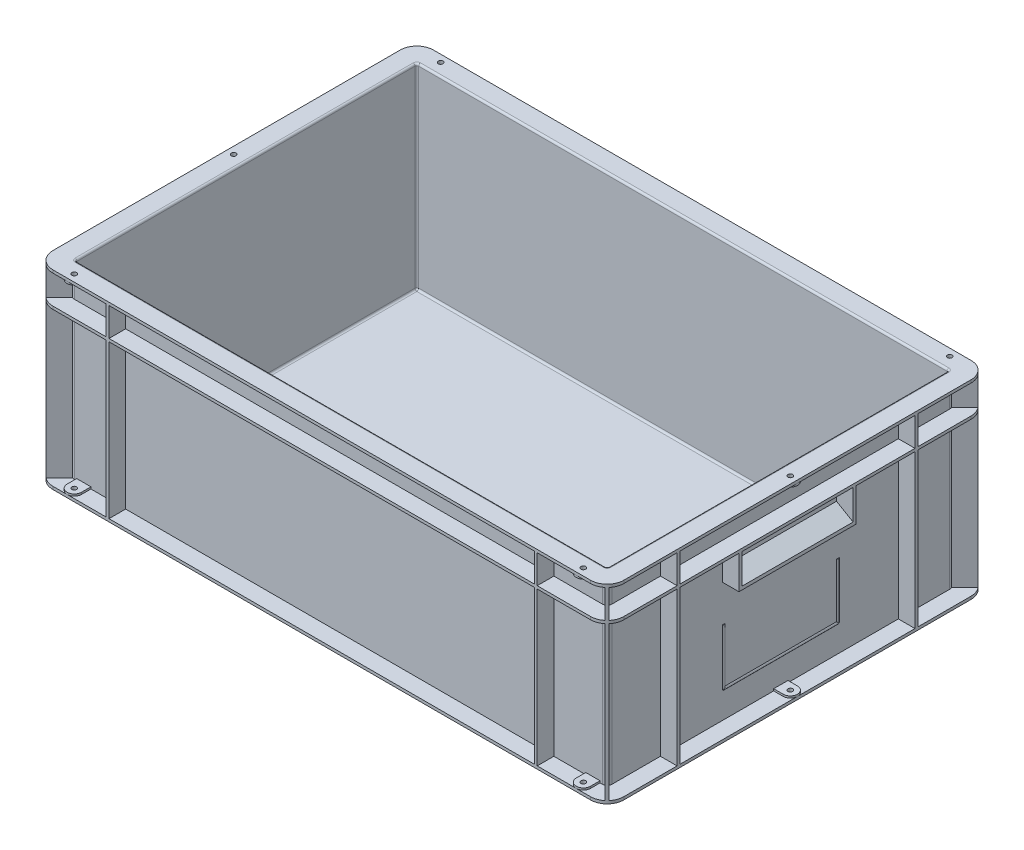
SolidWorks part; units mm, degrees
material "PTFE (général)"
ref_plane "Plan de face" through (0, 0, 0) normal (0, 0, 1) x (1, 0, 0)
ref_plane "Plan de dessus" through (0, 0, 0) normal (0, 1, 0) x (1, 0, 0)
ref_plane "Plan de côté" through (0, 0, 0) normal (1, 0, 0) x (0, 0, -1)
sketch "Esquisse vue de DESSUS" plane through (0, 0, 0) normal (0, 1, 0) x (1, 0, 0)
  line L0 (-300, 0) -> (300, 0) construction
  line L1 (-282.5, 200) -> (282.5, 200)
  line L2 (-300, 182.5) -> (-300, -182.5)
  line L3 (-282.5, -200) -> (282.5, -200)
  line L4 (300, 182.5) -> (300, -182.5)
  line L5 (-277.5, 182.5) -> (277.5, 182.5)
  line L6 (0, 200) -> (0, -200) construction
  line L7 (282.5, 177.5) -> (282.5, -177.5)
  line L8 (-277.5, -182.5) -> (277.5, -182.5)
  line L9 (-282.5, 177.5) -> (-282.5, -177.5)
  line L10 (-282.5, 182.5) -> (-294.8744, 194.8744) construction
  line L11 (-295.8895, 193.7682) -> (-281.9333, 179.812)
  line L12 (-225, 200) -> (-225, 182.5) construction
  line L13 (-226.5, 200) -> (-226.5, 182.5)
  line L14 (-293.7682, 195.8895) -> (-279.812, 181.9333)
  line L15 (-223.5, 200) -> (-223.5, 182.5)
  line L16 (-223.5, -200) -> (-223.5, -182.5)
  line L17 (-226.5, -200) -> (-226.5, -182.5)
  line L18 (295.8895, 193.7682) -> (281.9333, 179.812)
  line L19 (293.7682, 195.8895) -> (279.812, 181.9333)
  line L20 (-300, 125) -> (-282.5, 125) construction
  line L21 (-300, 126.5) -> (-282.5, 126.5)
  line L22 (-300, 123.5) -> (-282.5, 123.5)
  line L23 (-300, -126.5) -> (-282.5, -126.5)
  line L24 (-300, -123.5) -> (-282.5, -123.5)
  line L25 (300, -123.5) -> (282.5, -123.5)
  line L26 (300, -126.5) -> (282.5, -126.5)
  line L27 (293.7682, -195.8895) -> (279.812, -181.9333)
  line L28 (295.8895, -193.7682) -> (281.9333, -179.812)
  line L29 (226.5, -200) -> (226.5, -182.5)
  line L30 (223.5, -200) -> (223.5, -182.5)
  line L31 (300, 126.5) -> (282.5, 126.5)
  line L32 (300, 123.5) -> (282.5, 123.5)
  line L33 (-295.8895, -193.7682) -> (-281.9333, -179.812)
  line L34 (-293.7682, -195.8895) -> (-279.812, -181.9333)
  line L35 (223.5, 200) -> (223.5, 182.5)
  line L36 (226.5, 200) -> (226.5, 182.5)
  line L37 (-282.5, 182.5) -> (282.5, 182.5) construction
  line L38 (-282.5, 182.5) -> (-282.5, -182.5) construction
  line L39 (282.5, 182.5) -> (282.5, -182.5) construction
  line L40 (-282.5, -182.5) -> (282.5, -182.5) construction
  line L41 (282.5, 7.5) -> (292.5, 7.5)
  line L42 (292.5, -7.5) -> (282.5, -7.5)
  line L43 (260, 182.5) -> (260, 192.5)
  line L44 (275, 192.5) -> (275, 182.5)
  line L45 (275, -192.5) -> (275, -182.5)
  line L46 (260, -182.5) -> (260, -192.5)
  line L47 (-282.5, 7.5) -> (-292.5, 7.5)
  line L48 (-292.5, -7.5) -> (-282.5, -7.5)
  line L49 (-260, 182.5) -> (-260, 192.5)
  line L50 (-275, 192.5) -> (-275, 182.5)
  line L51 (-260, -182.5) -> (-260, -192.5)
  line L52 (-275, -192.5) -> (-275, -182.5)
  arc A0 (300, -182.5) -> (282.5, -200) centre (282.5, -182.5) cw
  arc A1 (282.5, 200) -> (300, 182.5) centre (282.5, 182.5) cw
  arc A2 (-300, 182.5) -> (-282.5, 200) centre (-282.5, 182.5) cw
  arc A3 (-282.5, -200) -> (-300, -182.5) centre (-282.5, -182.5) cw
  arc A4 (282.5, -177.5) -> (277.5, -182.5) centre (277.5, -177.5) cw
  arc A5 (277.5, 182.5) -> (282.5, 177.5) centre (277.5, 177.5) cw
  arc A6 (-282.5, 177.5) -> (-277.5, 182.5) centre (-277.5, 177.5) cw
  arc A7 (-282.5, -177.5) -> (-277.5, -182.5) centre (-277.5, -177.5) ccw
  arc A8 (292.5, 7.5) -> (292.5, -7.5) centre (292.5, 0) cw
  circle A9 centre (292.5, 0) radius 2.5
  arc A10 (260, 192.5) -> (275, 192.5) centre (267.5, 192.5) cw
  circle A11 centre (267.5, 192.5) radius 2.5
  arc A12 (-282.5, 182.5) -> (-282.5, 182.5) centre (-282.5, 182.5) cw construction
  arc A13 (282.5, 182.5) -> (282.5, 182.5) centre (282.5, 182.5) cw construction
  arc A14 (282.5, -182.5) -> (282.5, -182.5) centre (282.5, -182.5) cw construction
  arc A15 (-282.5, -182.5) -> (-282.5, -182.5) centre (-282.5, -182.5) cw construction
  circle A16 centre (267.5, -192.5) radius 2.5
  arc A17 (260, -192.5) -> (275, -192.5) centre (267.5, -192.5) ccw
  circle A18 centre (-292.5, 0) radius 2.5
  arc A19 (-292.5, 7.5) -> (-292.5, -7.5) centre (-292.5, 0) ccw
  circle A20 centre (-267.5, 192.5) radius 2.5
  arc A21 (-260, 192.5) -> (-275, 192.5) centre (-267.5, 192.5) ccw
  arc A22 (-260, -192.5) -> (-275, -192.5) centre (-267.5, -192.5) cw
  circle A23 centre (-267.5, -192.5) radius 2.5
  dimension "D3" = 17.5
  dimension "D10" = 5
  dimension "D12" = 5
  dimension "D1" = 600
  dimension "D2" = 400
  dimension "D4" = 17.5
  dimension "D5" = 3
  dimension "D6" = 75
  dimension "D7" = 3
  dimension "D8" = 3
  dimension "D9" = 75
  dimension "D11" = 15
  dimension "D13" = 32.5
sketch "Esquisse vue de FACE" plane through (0, 0, 0) normal (0, 0, 1) x (1, 0, 0)
  line L0 (0, 200) -> (0, -9) construction
  line L1 (-300, 200) -> (300, 200)
  line L2 (-300, 200) -> (-300, 0)
  line L3 (-300, 0) -> (300, 0)
  line L4 (300, 200) -> (300, 0)
  line L5 (-295.8895, 197) -> (-226.5, 197)
  line L6 (282.5, 0) -> (282.5, -9)
  line L7 (282.5, -9) -> (-282.5, -9)
  line L8 (-282.5, 0) -> (-282.5, -9)
  line L9 (-226.5, 197) -> (-226.5, 167)
  line L10 (-226.5, 167) -> (-295.8895, 167)
  line L11 (-295.8895, 167) -> (-295.8895, 197)
  line L12 (226.5, 164) -> (226.5, 3)
  line L13 (-295.8895, 164) -> (-226.5, 164)
  line L14 (-295.8895, 164) -> (-295.8895, 3)
  line L15 (-295.8895, 3) -> (-226.5, 3)
  line L16 (-226.5, 164) -> (-226.5, 3)
  line L17 (-223.5, 167) -> (223.5, 167)
  line L18 (-223.5, 167) -> (-223.5, 197)
  line L19 (-223.5, 197) -> (223.5, 197)
  line L20 (223.5, 167) -> (223.5, 197)
  line L21 (-223.5, 164) -> (223.5, 164)
  line L22 (-223.5, 164) -> (-223.5, 3)
  line L23 (-223.5, 3) -> (223.5, 3)
  line L24 (223.5, 164) -> (223.5, 3)
  line L25 (295.8895, 3) -> (226.5, 3)
  line L26 (295.8895, 164) -> (295.8895, 3)
  line L27 (295.8895, 164) -> (226.5, 164)
  line L28 (295.8895, 167) -> (295.8895, 197)
  line L29 (226.5, 167) -> (295.8895, 167)
  line L30 (226.5, 197) -> (226.5, 167)
  line L31 (295.8895, 197) -> (226.5, 197)
  line L32 (-300, 129) -> (-282.5, 129)
  line L33 (-282.5, 142.5677) -> (-300, 132.4641)
  line L34 (282.5, 164) -> (282.5, 129)
  line L35 (282.5, 139.1036) -> (300, 129)
  line L36 (282.5, 142.5677) -> (300, 132.4641)
  line L37 (300, 129) -> (282.5, 129)
  line L38 (-282.5, 139.1036) -> (-300, 129)
  line L41 (-282.5, 164) -> (-282.5, 129)
  line L42 (282.5, 195) -> (300, 195)
  line L43 (282.5, 5) -> (300, 5)
  dimension "D1" = 200
  dimension "D2" = 3
  dimension "D3" = 565
  dimension "D4" = 9
  dimension "D5" = 35
  dimension "D6" = 3
  dimension "D7" = 30
  dimension "D8" = 30
  dimension "D9" = 3
  dimension "D10" = 3
  dimension "D11" = 5
  dimension "D12" = 5
sketch "Esquisse vue de COTE" plane through (0, 0, 0) normal (1, 0, 0) x (0, 0, -1)
  line L0 (0, 200) -> (0, 11.0644) construction
  line L1 (-200, 200) -> (200, 200)
  line L2 (-200, 200) -> (-200, 0)
  line L3 (-200, 0) -> (200, 0)
  line L4 (200, 200) -> (200, 0)
  line L5 (193.7682, 167) -> (193.7682, 197)
  line L6 (-193.7682, 3) -> (-126.5, 3)
  line L7 (-193.7682, 3) -> (-193.7682, 164)
  line L8 (-193.7682, 164) -> (-126.5, 164)
  line L9 (-126.5, 3) -> (-126.5, 164)
  line L10 (-193.7682, 167) -> (-126.5, 167)
  line L11 (-193.7682, 167) -> (-193.7682, 197)
  line L12 (-193.7682, 197) -> (-126.5, 197)
  line L13 (-126.5, 167) -> (-126.5, 197)
  line L14 (-123.5, 164) -> (123.5, 164)
  line L15 (-123.5, 164) -> (-123.5, 3)
  line L16 (-123.5, 3) -> (123.5, 3)
  line L17 (123.5, 164) -> (123.5, 3)
  line L18 (-123.5, 167) -> (123.5, 167)
  line L19 (-123.5, 167) -> (-123.5, 197)
  line L20 (-123.5, 197) -> (123.5, 197)
  line L21 (123.5, 167) -> (123.5, 197)
  line L22 (193.7682, 197) -> (126.5, 197)
  line L23 (126.5, 167) -> (126.5, 197)
  line L24 (193.7682, 167) -> (126.5, 167)
  line L25 (193.7682, 3) -> (193.7682, 164)
  line L26 (193.7682, 3) -> (126.5, 3)
  line L27 (126.5, 3) -> (126.5, 164)
  line L28 (193.7682, 164) -> (126.5, 164)
  line L29 (-58.5, 164) -> (-58.5, 129)
  line L30 (-61.5, 129) -> (61.5, 129)
  line L31 (-61.5, 129) -> (-61.5, 164)
  line L32 (-58.5, 142.5677) -> (58.5, 142.5677)
  line L33 (61.5, 129) -> (61.5, 164)
  line L34 (58.5, 129) -> (58.5, 164)
  line L35 (-60, 164) -> (-60, 131.7579) construction
  line L36 (-58.5, 132.4641) -> (58.5, 132.4641)
  line L37 (58.5, 90) -> (61.5, 90)
  line L38 (-61.5, 90) -> (-58.5, 90)
  line L39 (-61.5, 90) -> (-61.5, 30)
  line L40 (-61.5, 30) -> (61.5, 30)
  line L41 (61.5, 90) -> (61.5, 30)
  line L42 (60, 90) -> (60, 31.5) construction
  line L43 (58.5, 90) -> (58.5, 33)
  line L44 (58.5, 33) -> (-58.5, 33)
  line L45 (-58.5, 90) -> (-58.5, 33)
  line L46 (60, 31.5) -> (-60, 31.5) construction
  line L47 (-60, 90) -> (-60, 31.5) construction
  line L48 (58.5, 33) -> (61.5, 30) construction
  line L49 (61.5, 30) -> (61.5195, 20.0006)
  dimension "D1" = 3
  dimension "D2" = 120
  dimension "D3" = 3
  dimension "D4" = 30
  dimension "D5" = 60
sketch "Esquisse4" plane through (0, 0, 0) normal (0, 1, 0) x (1, 0, 0)
  line L0 (-277.5, 182.5) -> (277.5, 182.5) construction
  line L1 (282.5, 177.5) -> (282.5, -177.5) construction
  line L2 (-277.5, -182.5) -> (277.5, -182.5) construction
  line L3 (-282.5, 177.5) -> (-282.5, -177.5) construction
  line L4 (-277.5, 182.5) -> (277.5, 182.5)
  line L5 (282.5, 177.5) -> (282.5, -177.5)
  line L6 (-277.5, -182.5) -> (277.5, -182.5)
  line L7 (-282.5, 177.5) -> (-282.5, -177.5)
  arc A0 (-277.5, 182.5) -> (-282.5, 177.5) centre (-277.5, 177.5) ccw construction
  arc A1 (282.5, 177.5) -> (277.5, 182.5) centre (277.5, 177.5) ccw construction
  arc A2 (277.5, -182.5) -> (282.5, -177.5) centre (277.5, -177.5) ccw construction
  arc A3 (-282.5, -177.5) -> (-277.5, -182.5) centre (-277.5, -177.5) ccw construction
  arc A4 (-277.5, 182.5) -> (-282.5, 177.5) centre (-277.5, 177.5) ccw
  arc A5 (282.5, 177.5) -> (277.5, 182.5) centre (277.5, 177.5) ccw
  arc A6 (277.5, -182.5) -> (282.5, -177.5) centre (277.5, -177.5) ccw
  arc A7 (-282.5, -177.5) -> (-277.5, -182.5) centre (-277.5, -177.5) ccw
extrude "Extrusion2" add sketch "Esquisse4" against normal up to vertex (9 mm away) and the other way up to vertex (200 mm away) up to point (-282.5, -9, 0) other way up to point (-300, 200, 0)
shell "Coque1" thickness 3 removed face at (0, 200, 0)
sketch "Esquisse5" plane through (0, 0, 0) normal (0, 1, 0) x (1, 0, 0)
  line L0 (-300, 182.5) -> (-300, -182.5) construction
  line L1 (-282.5, 200) -> (282.5, 200) construction
  line L2 (300, 182.5) -> (300, -182.5) construction
  line L3 (-282.5, -200) -> (282.5, -200) construction
  line L4 (-300, 182.5) -> (-300, -182.5)
  line L5 (-282.5, 200) -> (282.5, 200)
  line L6 (300, 182.5) -> (300, -182.5)
  line L7 (-282.5, -200) -> (282.5, -200)
  line L8 (279.5, -177.5) -> (279.5, 177.5) construction
  line L9 (277.5, 179.5) -> (-277.5, 179.5) construction
  line L10 (-279.5, 177.5) -> (-279.5, -177.5) construction
  line L11 (-277.5, -179.5) -> (277.5, -179.5) construction
  line L12 (279.5, -177.5) -> (279.5, 177.5)
  line L13 (277.5, 179.5) -> (-277.5, 179.5)
  line L14 (-279.5, 177.5) -> (-279.5, -177.5)
  line L15 (-277.5, -179.5) -> (277.5, -179.5)
  arc A0 (-300, -182.5) -> (-282.5, -200) centre (-282.5, -182.5) ccw construction
  arc A1 (-282.5, 200) -> (-300, 182.5) centre (-282.5, 182.5) ccw construction
  arc A2 (300, 182.5) -> (282.5, 200) centre (282.5, 182.5) ccw construction
  arc A3 (282.5, -200) -> (300, -182.5) centre (282.5, -182.5) ccw construction
  arc A4 (-300, -182.5) -> (-282.5, -200) centre (-282.5, -182.5) ccw
  arc A5 (-282.5, 200) -> (-300, 182.5) centre (-282.5, 182.5) ccw
  arc A6 (300, 182.5) -> (282.5, 200) centre (282.5, 182.5) ccw
  arc A7 (282.5, -200) -> (300, -182.5) centre (282.5, -182.5) ccw
  arc A8 (277.5, -179.5) -> (279.5, -177.5) centre (277.5, -177.5) ccw construction
  arc A9 (279.5, 177.5) -> (277.5, 179.5) centre (277.5, 177.5) ccw construction
  arc A10 (-277.5, 179.5) -> (-279.5, 177.5) centre (-277.5, 177.5) ccw construction
  arc A11 (-279.5, -177.5) -> (-277.5, -179.5) centre (-277.5, -177.5) ccw construction
  arc A12 (277.5, -179.5) -> (279.5, -177.5) centre (277.5, -177.5) ccw
  arc A13 (279.5, 177.5) -> (277.5, 179.5) centre (277.5, 177.5) ccw
  arc A14 (-277.5, 179.5) -> (-279.5, 177.5) centre (-277.5, 177.5) ccw
  arc A15 (-279.5, -177.5) -> (-277.5, -179.5) centre (-277.5, -177.5) ccw
extrude "Extrusion3" add sketch "Esquisse5" along normal up to vertex (200 mm away) from vertex up to point (-300, 200, 0) starting at point (-295.8895, 197, 0)
extrude "Extrusion4" add sketch "Esquisse5<2>" along normal up to vertex (3 mm away) up to point (-295.8895, 3, 0)
sketch "Esquisse5<2>" plane through (0, 0, 0) normal (0, 1, 0) x (1, 0, 0) same geometry as "Esquisse5"
extrude "Extrusion7" add sketch "Esquisse5<4>" along normal up to vertex (167 mm away) from vertex up to point (295.8895, 167, 0) starting at point (295.8895, 164, 0)
sketch "Esquisse5<4>" plane through (0, 0, 0) normal (0, 1, 0) x (1, 0, 0) same geometry as "Esquisse5"
sketch "Esquisse6" plane through (0, 0, 0) normal (0, 1, 0) x (1, 0, 0)
  line L0 (-300, 123.5) -> (-282.5, 123.5) construction
  line L1 (-300, 182.5) -> (-300, -182.5) construction
  line L2 (-300, 126.5) -> (-282.5, 126.5) construction
  line L3 (-282.5, 177.5) -> (-282.5, -177.5) construction
  line L4 (-277.5, 182.5) -> (277.5, 182.5) construction
  line L5 (-223.5, 200) -> (-223.5, 182.5) construction
  line L6 (-282.5, 200) -> (282.5, 200) construction
  line L7 (-226.5, 200) -> (-226.5, 182.5) construction
  line L8 (-295.8895, 193.7682) -> (-281.9333, 179.812) construction
  line L9 (-293.7682, 195.8895) -> (-279.812, 181.9333) construction
  line L10 (-300, 123.5) -> (-282.5, 123.5)
  line L11 (-300, 126.5) -> (-300, 123.5)
  line L12 (-300, 126.5) -> (-282.5, 126.5)
  line L13 (-282.5, 126.5) -> (-282.5, 123.5)
  line L14 (-226.5, 182.5) -> (-223.5, 182.5)
  line L15 (-223.5, 200) -> (-223.5, 182.5)
  line L16 (-226.5, 200) -> (-223.5, 200)
  line L17 (-226.5, 200) -> (-226.5, 182.5)
  line L18 (-295.8895, 193.7682) -> (-281.9333, 179.812)
  line L19 (-293.7682, 195.8895) -> (-279.812, 181.9333)
  arc A0 (-277.5, 182.5) -> (-282.5, 177.5) centre (-277.5, 177.5) ccw construction
  arc A1 (-282.5, 200) -> (-300, 182.5) centre (-282.5, 182.5) ccw construction
  arc A2 (-279.812, 181.9333) -> (-281.9333, 179.812) centre (-277.5, 177.5) ccw
  arc A3 (-293.7682, 195.8895) -> (-295.8895, 193.7682) centre (-282.5, 182.5) ccw
extrude "Extrusion5" add sketch "Esquisse6" along normal up to vertex (200 mm away) up to point (-300, 200, 0)
mirror "Symétrie1" about plane through (0, 0, 0) normal (1, 0, 0) of "Extrusion5"
mirror "Symétrie2" about plane through (0, 0, 0) normal (0, 0, 1) of "Symétrie1", "Extrusion5"
sketch "Esquisse7" plane through (0, 0, 0) normal (1, 0, 0) x (0, 0, -1)
  line L0 (-58.5, 164) -> (-58.5, 129) construction
  line L1 (-61.5, 129) -> (-61.5, 164) construction
  line L2 (-61.5, 129) -> (61.5, 129) construction
  line L3 (58.5, 129) -> (58.5, 164) construction
  line L4 (61.5, 129) -> (61.5, 164) construction
  line L5 (-58.5, 164) -> (-58.5, 129)
  line L6 (-61.5, 129) -> (-61.5, 164)
  line L7 (-61.5, 129) -> (-58.5, 129)
  line L8 (58.5, 129) -> (58.5, 164)
  line L9 (61.5, 129) -> (61.5, 164)
  line L10 (58.5, 129) -> (61.5, 129)
  line L11 (-123.5, 164) -> (123.5, 164) construction
  line L12 (-61.5, 164) -> (-58.5, 164)
  line L13 (58.5, 164) -> (61.5, 164)
extrude "Extrusion6" add sketch "Esquisse7" along normal up to vertex (300 mm away) from vertex up to point (300, 0, -123.5) starting at point (282.5, 0, 0)
extrude "Extrusion13" add sketch "Esquisse7<2>" against normal up to vertex (300 mm away) from vertex up to point (-300, 164, 123.5) starting at point (-282.5, 197, 123.5)
sketch "Esquisse7<2>" plane through (0, 0, 0) normal (1, 0, 0) x (0, 0, -1) same geometry as "Esquisse7"
sketch "Esquisse8" plane through (0, 0, 0) normal (0, 0, 1) x (1, 0, 0)
  line L0 (282.5, 164) -> (282.5, 129) construction
  line L2 (282.5, 142.5677) -> (300, 132.4641) construction
  line L3 (282.5, 139.1036) -> (300, 129) construction
  line L4 (282.5, 142.5677) -> (282.5, 139.1036)
  line L5 (300, 132.4641) -> (300, 129)
  line L6 (282.5, 142.5677) -> (300, 132.4641)
  line L7 (282.5, 139.1036) -> (300, 129)
extrude "Extrusion8" add sketch "Esquisse8" against normal up to vertex (58.5 mm away) and the other way up to vertex (58.5 mm away) up to point (300, 129, -58.5) other way up to point (300, 129, 58.5)
mirror "Symétrie6" about plane through (0, 0, 0) normal (1, 0, 0) of "Extrusion8"
sketch "Esquisse9" plane through (0, 0, 0) normal (0, 1, 0) x (1, 0, 0)
  line L0 (282.5, 177.5) -> (282.5, -177.5) construction
  line L1 (-277.5, 182.5) -> (277.5, 182.5) construction
  line L2 (-282.5, 177.5) -> (-282.5, -177.5) construction
  line L3 (-277.5, -182.5) -> (277.5, -182.5) construction
  line L4 (-275, -192.5) -> (-275, -182.5) construction
  line L5 (-260, -182.5) -> (-260, -192.5) construction
  line L6 (-292.5, -7.5) -> (-282.5, -7.5) construction
  line L7 (-282.5, 7.5) -> (-292.5, 7.5) construction
  line L8 (-275, 192.5) -> (-275, 182.5) construction
  line L9 (-260, 182.5) -> (-260, 192.5) construction
  line L10 (275, 192.5) -> (275, 182.5) construction
  line L11 (260, 182.5) -> (260, 192.5) construction
  line L12 (292.5, -7.5) -> (282.5, -7.5) construction
  line L13 (282.5, 7.5) -> (292.5, 7.5) construction
  line L14 (275, -192.5) -> (275, -182.5) construction
  line L15 (260, -182.5) -> (260, -192.5) construction
  line L16 (282.5, 7.5) -> (282.5, -7.5)
  line L17 (-275, 182.5) -> (-260, 182.5)
  line L18 (-282.5, 7.5) -> (-282.5, -7.5)
  line L19 (-275, -182.5) -> (-260, -182.5)
  line L20 (-275, -192.5) -> (-275, -182.5)
  line L21 (-260, -182.5) -> (-260, -192.5)
  line L22 (-292.5, -7.5) -> (-282.5, -7.5)
  line L23 (-282.5, 7.5) -> (-292.5, 7.5)
  line L24 (-275, 192.5) -> (-275, 182.5)
  line L25 (-260, 182.5) -> (-260, 192.5)
  line L26 (275, 192.5) -> (275, 182.5)
  line L27 (260, 182.5) -> (260, 192.5)
  line L28 (292.5, -7.5) -> (282.5, -7.5)
  line L29 (282.5, 7.5) -> (292.5, 7.5)
  line L30 (275, -192.5) -> (275, -182.5)
  line L31 (260, -182.5) -> (260, -192.5)
  line L32 (260, 182.5) -> (275, 182.5)
  line L33 (260, -182.5) -> (275, -182.5)
  arc A0 (-275, -192.5) -> (-260, -192.5) centre (-267.5, -192.5) ccw construction
  arc A1 (-292.5, 7.5) -> (-292.5, -7.5) centre (-292.5, 0) ccw construction
  arc A2 (-260, 192.5) -> (-275, 192.5) centre (-267.5, 192.5) ccw construction
  arc A3 (275, 192.5) -> (260, 192.5) centre (267.5, 192.5) ccw construction
  arc A4 (292.5, -7.5) -> (292.5, 7.5) centre (292.5, 0) ccw construction
  arc A5 (260, -192.5) -> (275, -192.5) centre (267.5, -192.5) ccw construction
  arc A6 (-275, -192.5) -> (-260, -192.5) centre (-267.5, -192.5) ccw
  arc A7 (-292.5, 7.5) -> (-292.5, -7.5) centre (-292.5, 0) ccw
  arc A8 (-260, 192.5) -> (-275, 192.5) centre (-267.5, 192.5) ccw
  arc A9 (275, 192.5) -> (260, 192.5) centre (267.5, 192.5) ccw
  arc A10 (292.5, -7.5) -> (292.5, 7.5) centre (292.5, 0) ccw
  arc A11 (260, -192.5) -> (275, -192.5) centre (267.5, -192.5) ccw
extrude "Extrusion9" add sketch "Esquisse9" along normal up to vertex (5 mm away) up to point (282.5, 5, 0)
extrude "Extrusion10" add sketch "Esquisse9<2>" along normal up to vertex (200 mm away) from vertex up to point (300, 200, 0) starting at point (282.5, 195, 0)
sketch "Esquisse9<2>" plane through (0, 0, 0) normal (0, 1, 0) x (1, 0, 0) same geometry as "Esquisse9"
sketch "Esquisse10" plane through (0, 0, 0) normal (0, 1, 0) x (1, 0, 0)
  circle A0 centre (267.5, -192.5) radius 2.5 construction
  circle A1 centre (292.5, 0) radius 2.5 construction
  circle A2 centre (267.5, 192.5) radius 2.5 construction
  circle A3 centre (267.5, -192.5) radius 2.5
  circle A4 centre (292.5, 0) radius 2.5
  circle A5 centre (267.5, 192.5) radius 2.5
  circle A6 centre (-267.5, 192.5) radius 2.5 construction
  circle A7 centre (-292.5, 0) radius 2.5 construction
  circle A8 centre (-267.5, -192.5) radius 2.5 construction
  circle A9 centre (-267.5, 192.5) radius 2.5
  circle A10 centre (-292.5, 0) radius 2.5
  circle A11 centre (-267.5, -192.5) radius 2.5
extrude "Extrusion11" cut sketch "Esquisse10" along normal up to vertex (5 mm away) up to point (282.5, 5, -7.5)
extrude "Extrusion12" cut sketch "Esquisse10<2>" along normal through all from vertex starting at point (292.5, 195, 7.5)
sketch "Esquisse10<2>" plane through (0, 0, 0) normal (0, 1, 0) x (1, 0, 0) same geometry as "Esquisse10"
sketch "Esquisse11" plane through (0, 0, 0) normal (0, 0, 1) x (1, 0, 0)
  line L0 (282.5, 33) -> (282.5, 30)
  line L1 (282.5, 164) -> (282.5, 3) construction
  arc A0 (282.5, 33) -> (282.5, 30) centre (281.375, 31.5) cw
  dimension "D1" = 0.75
extrude "Extrusion14" add sketch "Esquisse11" against normal up to vertex (60 mm away) and the other way up to vertex (60 mm away) up to point (0, 31.5, -60) other way up to point (0, 31.5, 60)
sketch "Esquisse12" plane through (0, 0, 0) normal (0, 1, 0) x (1, 0, 0)
  line L0 (282.5, -61.5) -> (282.5, -58.5)
  line L1 (282.5, 60) -> (282.5, -60) construction
  arc A0 (282.5, -61.5) -> (282.5, -58.5) centre (281.375, -60) ccw
  dimension "D1" = 0.75
extrude "Extrusion15" add sketch "Esquisse12" along normal up to vertex (90 mm away) from vertex up to point (0, 90, 61.5) starting at point (0, 31.5, 60)
sketch "Esquisse13" plane through (0, 0, 60) normal (0, 0, 1) x (1, 0, 0)
  line L0 (181.9751, 31.5) -> (183.446, 31.5) construction
  line L3 (283.25, 31.5) -> (282.5, 31.5)
  line L4 (282.5, 31.5) -> (282.5, 30)
  line L5 (283.25, 31.5) -> (282.5, 31.5)
  line L6 (282.5, 31.5) -> (282.5, 30)
  arc A1 (282.5, 30) -> (283.25, 31.5) centre (281.375, 31.5) ccw
  arc A2 (282.5, 30) -> (283.25, 31.5) centre (281.375, 31.5) ccw
  dimension "D1" = 0
revolve "Révolution1" add sketch "Esquisse13" angle 90 about L0 reverse direction yes
mirror "Symétrie7" about plane through (0, 0, 0) normal (0, 0, 1) of "Révolution1", "Extrusion15"
fillet "Congé1" radius 2 32 edges at (-278.9142, 200, -178.9142) (0, 200, -179.5) (278.9142, 200, -178.9142) (279.5, 200, 0) (278.9142, 200, 178.9142) (0, 200, 179.5) (-278.9142, 200, 178.9142) (-279.5, 200, 0) (-278.9142, -6, -178.9142) (0, -6, -179.5) (278.9142, -6, -178.9142) (279.5, -6, 0) (278.9142, -6, 178.9142) (0, -6, 179.5) (-278.9142, -6, 178.9142) (-279.5, -6, 0) (281.0355, -9, 181.0355) (0, -9, 182.5) (-281.0355, -9, 181.0355) (-282.5, -9, 0) (-281.0355, -9, -181.0355) (0, -9, -182.5) (281.0355, -9, -181.0355) (282.5, -9, 0) (281.0355, 0, -181.0355) (0, 0, -182.5) (-281.0355, 0, -181.0355) (-282.5, 0, 0) (-281.0355, 0, 181.0355) (0, 0, 182.5) (281.0355, 0, 181.0355) (282.5, 0, 0)
